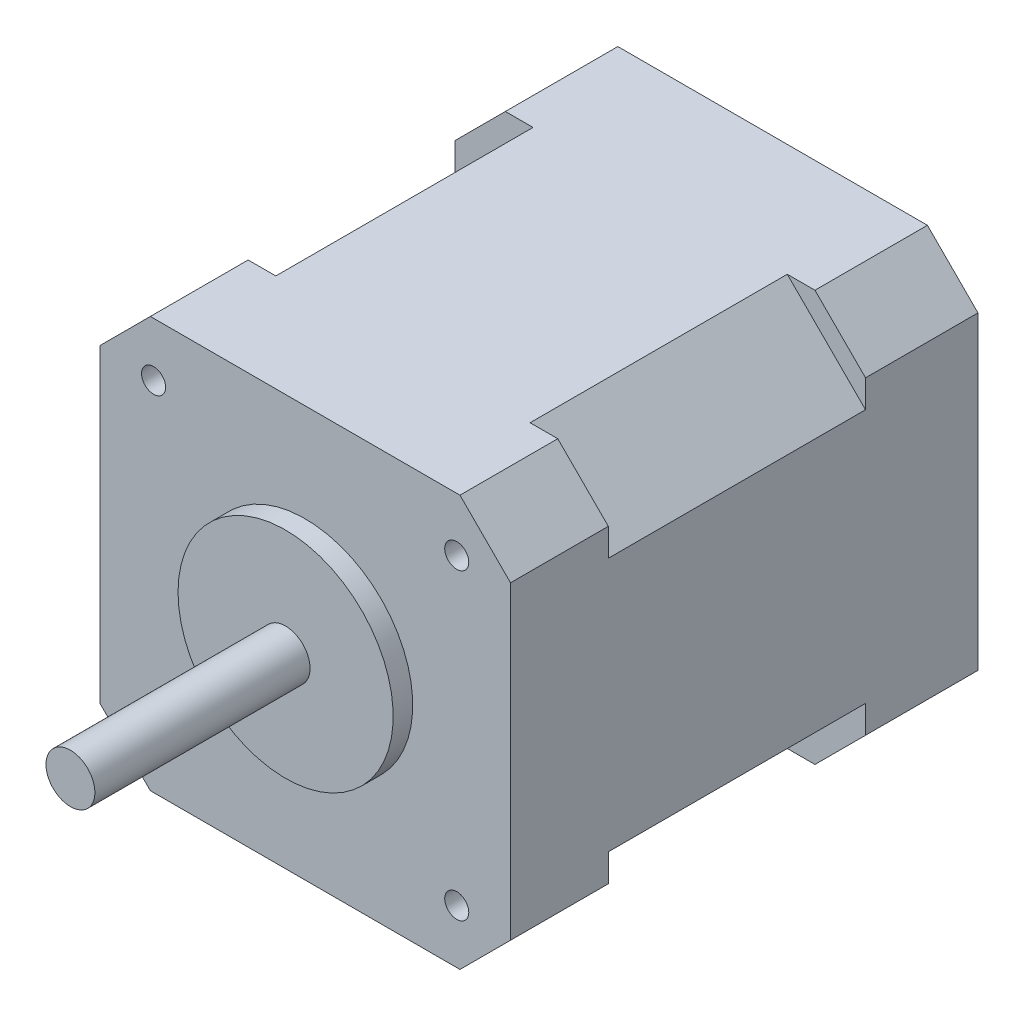
SolidWorks part; units mm, degrees
ref_plane "Front Plane" through (0, 0, 0) normal (0, 0, 1) x (1, 0, 0)
ref_plane "Top Plane" through (0, 0, 0) normal (0, 1, 0) x (1, 0, 0)
ref_plane "Right Plane" through (0, 0, 0) normal (1, 0, 0) x (0, 0, -1)
ref_plane "Plane1" through (0, 0, 0) normal (0, 0, -1) x (-1, 0, 0)
sketch "Sketch1" plane through (0, 0, 0) normal (0, 0, -1) x (-1, 0, 0)
  line L0 (-15.8284, 21) -> (-21, 15.8284)
  line L1 (-21, 15.8284) -> (-21, -15.8284)
  line L2 (-21, -15.8284) -> (-15.8284, -21)
  line L3 (-15.8284, -21) -> (15.8284, -21)
  line L4 (15.8284, -21) -> (21, -15.8284)
  line L5 (21, -15.8284) -> (21, 15.8284)
  line L6 (21, 15.8284) -> (15.8284, 21)
  line L7 (15.8284, 21) -> (-15.8284, 21)
extrude "Boss-Extrude1" add sketch "Sketch1" against normal blind 11.5
sketch "Sketch2" plane through (0, 0, 11.5) normal (0, 0, 1) x (1, 0, 0)
  line L0 (13, -21) -> (-13, -21)
  line L1 (-13, -21) -> (-21, -13)
  line L2 (-21, -13) -> (-21, 13)
  line L3 (-21, 13) -> (-13, 21)
  line L4 (-13, 21) -> (13, 21)
  line L5 (13, 21) -> (21, 13)
  line L6 (21, 13) -> (21, -13)
  line L7 (21, -13) -> (13, -21)
extrude "Boss-Extrude2" add sketch "Sketch2" along normal blind 26.3
sketch "Sketch3" plane through (0, 0, 37.8) normal (0, 0, 1) x (1, 0, 0)
  line L0 (15.8284, 21) -> (21, 15.8284)
  line L1 (21, 15.8284) -> (21, -15.8284)
  line L2 (21, -15.8284) -> (15.8284, -21)
  line L3 (15.8284, -21) -> (-15.8284, -21)
  line L4 (-15.8284, -21) -> (-21, -15.8284)
  line L5 (-21, -15.8284) -> (-21, 15.8284)
  line L6 (-21, 15.8284) -> (-15.8284, 21)
  line L7 (-15.8284, 21) -> (15.8284, 21)
extrude "Boss-Extrude3" add sketch "Sketch3" along normal blind 10
ref_plane "Plane2" through (0, 0, 3.65) normal (0, 0, 1) x (1, 0, 0)
sketch "Sketch4" plane through (0, 0, 3.65) normal (0, 0, 1) x (1, 0, 0)
  line L0 (-31, 1.25) -> (-31, 0.65)
  line L1 (-31, 0.65) -> (-21, 0.65)
  line L2 (-21, 0.65) -> (-21, 1.25)
  line L3 (-21, 1.25) -> (-31, 1.25)
  line L4 (-31, 0.65) -> (-21, 0.65) construction
revolve "Revolve1" add sketch "Sketch4" angle 360 about L4 reverse direction yes
sketch "Sketch5" plane through (0, 0, 3.65) normal (0, 0, 1) x (1, 0, 0)
  line L0 (-31, -0.05) -> (-31, -0.65)
  line L1 (-31, -0.65) -> (-21, -0.65)
  line L2 (-21, -0.65) -> (-21, -0.05)
  line L3 (-21, -0.05) -> (-31, -0.05)
  line L4 (-31, -0.65) -> (-21, -0.65) construction
revolve "Revolve2" add sketch "Sketch5" angle 360 about L4 reverse direction yes
ref_plane "Plane3" through (0, 0, 4.95) normal (0, 0, 1) x (1, 0, 0)
sketch "Sketch6" plane through (0, 0, 4.95) normal (0, 0, 1) x (1, 0, 0)
  line L0 (-31, -0.05) -> (-31, -0.65)
  line L1 (-31, -0.65) -> (-21, -0.65)
  line L2 (-21, -0.65) -> (-21, -0.05)
  line L3 (-21, -0.05) -> (-31, -0.05)
  line L4 (-31, -0.65) -> (-21, -0.65) construction
revolve "Revolve3" add sketch "Sketch6" angle 360 about L4 reverse direction yes
sketch "Sketch7" plane through (0, 0, 4.95) normal (0, 0, 1) x (1, 0, 0)
  line L0 (-31, 1.25) -> (-31, 0.65)
  line L1 (-31, 0.65) -> (-21, 0.65)
  line L2 (-21, 0.65) -> (-21, 1.25)
  line L3 (-21, 1.25) -> (-31, 1.25)
  line L4 (-31, 0.65) -> (-21, 0.65) construction
revolve "Revolve4" add sketch "Sketch7" angle 360 about L4 reverse direction yes
ref_plane "Plane4" through (0, 0, 0) normal (0, -1, 0) x (1, 0, 0)
sketch "Sketch8" plane through (0, 0, 0) normal (0, -1, 0) x (1, 0, 0)
  line L0 (2.5, 71.8) -> (0, 71.8)
  line L1 (0, 71.8) -> (0, 47.8)
  line L2 (0, 47.8) -> (11, 47.8)
  line L3 (11, 47.8) -> (11, 49.8)
  line L4 (11, 49.8) -> (2.5, 49.8)
  line L5 (2.5, 49.8) -> (2.5, 71.8)
  line L6 (0, 71.8) -> (0, 47.8) construction
revolve "Revolve5" add sketch "Sketch8" angle 360 about L6 reverse direction yes
hole_wizard "Hole1" positions "Sketch10" profile "Sketch9" legacy
sketch "Sketch10" plane through (0, 0, 47.8) normal (0, 0, 1) x (1, 0, 0)
  point P0 (-15.5, 15.5)
sketch "Sketch9" plane through (-15.5, 15.5, 47.8) normal (1, 0, 0) x (0, -1, 0)
  line L0 (0, 0) -> (0, 5)
  line L1 (0, 5) -> (1.2295, 5)
  line L2 (1.2295, 5) -> (1.2295, 0)
  line L3 (1.2295, 0) -> (0, 0)
  line L4 (0, 110) -> (0, -10) construction
  dimension "Diameter" = 2.459
  dimension "Depth" = 5
hole_wizard "Hole2" positions "Sketch12" profile "Sketch11" legacy
sketch "Sketch12" plane through (0, 0, 47.8) normal (0, 0, 1) x (1, 0, 0)
  point P0 (-15.5, -15.5)
sketch "Sketch11" plane through (-15.5, -15.5, 47.8) normal (1, 0, 0) x (0, -1, 0)
  line L0 (0, 0) -> (0, 5)
  line L1 (0, 5) -> (1.2295, 5)
  line L2 (1.2295, 5) -> (1.2295, 0)
  line L3 (1.2295, 0) -> (0, 0)
  line L4 (0, 110) -> (0, -10) construction
  dimension "Diameter" = 2.459
  dimension "Depth" = 5
hole_wizard "Hole3" positions "Sketch14" profile "Sketch13" legacy
sketch "Sketch14" plane through (0, 0, 47.8) normal (0, 0, 1) x (1, 0, 0)
  point P0 (15.5, 15.5)
sketch "Sketch13" plane through (15.5, 15.5, 47.8) normal (1, 0, 0) x (0, -1, 0)
  line L0 (0, 0) -> (0, 5)
  line L1 (0, 5) -> (1.2295, 5)
  line L2 (1.2295, 5) -> (1.2295, 0)
  line L3 (1.2295, 0) -> (0, 0)
  line L4 (0, 110) -> (0, -10) construction
  dimension "Diameter" = 2.459
  dimension "Depth" = 5
hole_wizard "Hole4" positions "Sketch16" profile "Sketch15" legacy
sketch "Sketch16" plane through (0, 0, 47.8) normal (0, 0, 1) x (1, 0, 0)
  point P0 (15.5, -15.5)
sketch "Sketch15" plane through (15.5, -15.5, 47.8) normal (1, 0, 0) x (0, -1, 0)
  line L0 (0, 0) -> (0, 5)
  line L1 (0, 5) -> (1.2295, 5)
  line L2 (1.2295, 5) -> (1.2295, 0)
  line L3 (1.2295, 0) -> (0, 0)
  line L4 (0, 110) -> (0, -10) construction
  dimension "Diameter" = 2.459
  dimension "Depth" = 5
